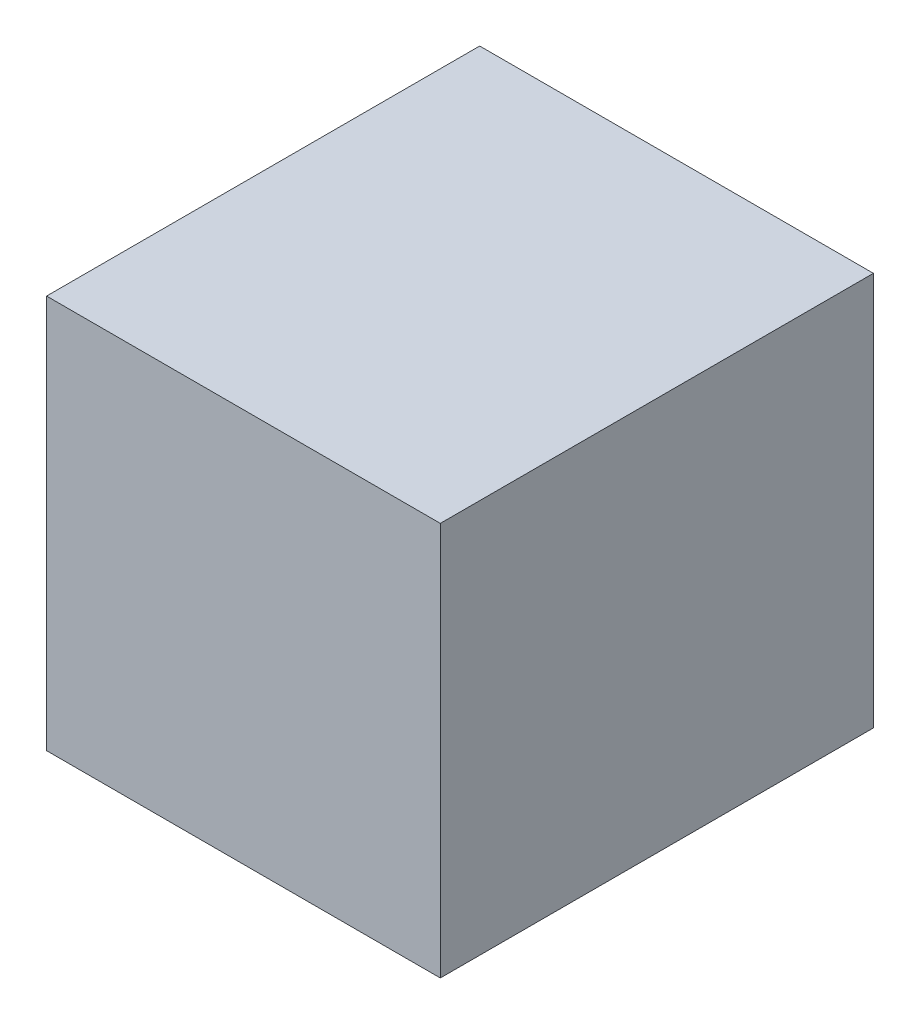
SolidWorks part; units mm, degrees
ref_plane "Front Plane" through (0, 0, 0) normal (1, 0, 0) x (0, 1, 0)
ref_plane "Top Plane" through (0, 0, 0) normal (0, 0, 1) x (0, 1, 0)
ref_plane "Right Plane" through (0, 0, 0) normal (0, 1, 0) x (-1, 0, 0)
sketch "Sketch1" plane through (0, 0, 0) normal (0, 0, 1) x (0, 1, 0)
  line L1 (-20, -20) -> (20, -20)
  line L2 (-20, -20) -> (-20, 20)
  line L3 (-20, 20) -> (20, 20)
  line L4 (20, -20) -> (20, 20)
  line L5 (-20, -20) -> (20, 20) construction
  line L6 (-20, 20) -> (20, -20) construction
  point P0 (0, 0)
extrude "Block" add sketch "Sketch1" along normal blind 44
sketch "Sketch2" plane through (0, 0, 0) normal (0, 1, 0) x (-1, 0, 0)
  line L0 (0, -0.5) -> (-4.3, -0.5)
  line L1 (-4.3, -0.5) -> (-3.8, 0)
  line L2 (-3.8, 0) -> (-3.4, 0.4)
  line L3 (-3.4, 0.4) -> (-3.4, 36)
  line L4 (-3.4, 36) -> (0, 36)
  line L5 (0, 36) -> (0, -0.5)
  line L6 (0, -200) -> (0, 200) construction
revolve "Hole" cut sketch "Sketch2" angle 360 about L6
sketch "Sketch3" plane through (0, 0, 0) normal (0, 1, 0) x (-1, 0, 0)
  line L0 (0, -0.5) -> (-5.5, -0.5)
  line L1 (-5.5, -0.5) -> (-5.5, 36)
  line L2 (-5.5, 36) -> (0, 36)
  line L3 (0, 36) -> (0, -0.5)
  line L4 (0, -200) -> (0, 200) construction
revolve "ClearanceHole" [suppressed] cut sketch "Sketch3" angle 360 about L4
sketch "Sketch4" plane through (0, 0, 0) normal (0, 1, 0) x (-1, 0, 0)
  line L0 (-4, -0.5) -> (-7.5, -0.5)
  line L1 (-7.5, -0.5) -> (-7.5, 0.3)
  line L2 (-7.5, 0.3) -> (-4, 0.3)
  line L3 (-4, 0.3) -> (-4, -0.5)
  line L4 (0, -200) -> (0, 200) construction
revolve "InsertGroove" cut sketch "Sketch4" angle 360 about L4
